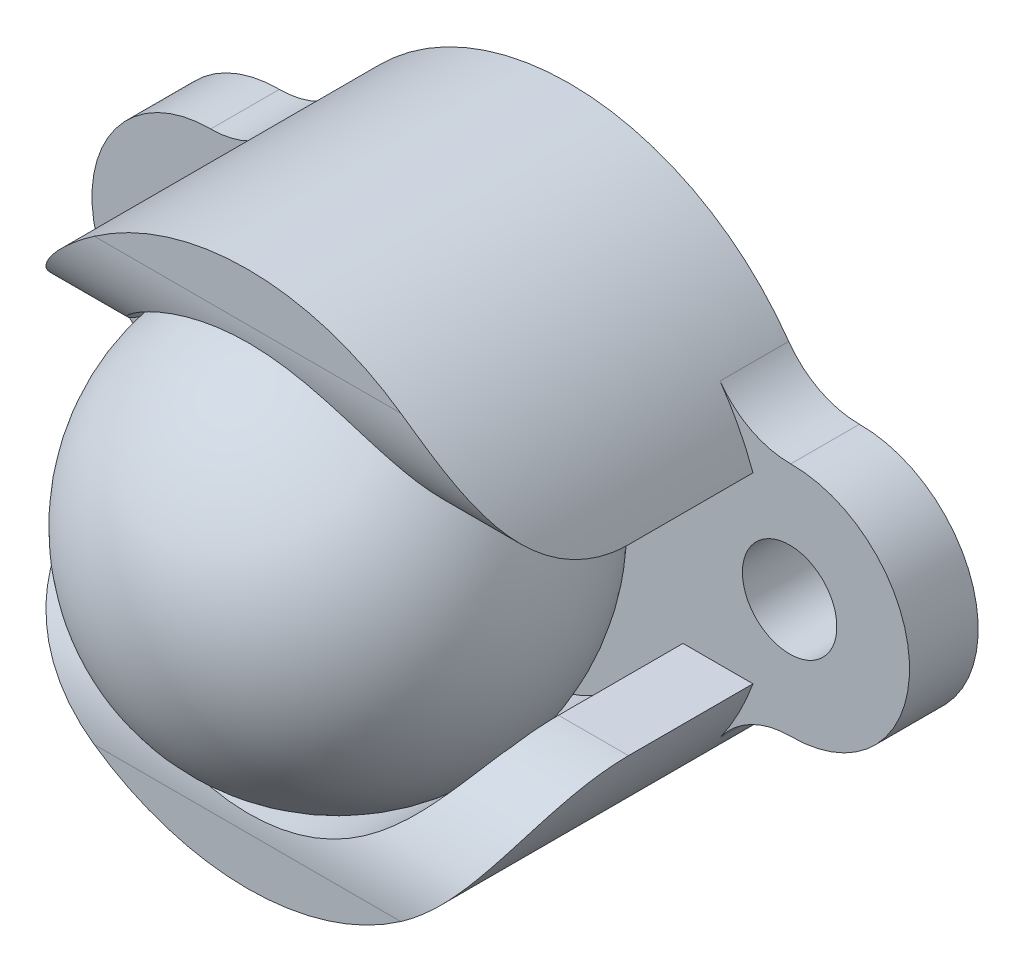
SolidWorks part; units mm, degrees
ref_plane "Front" through (0, 0, 0) normal (0, 0, 1) x (1, 0, 0)
ref_plane "Top" through (0, 0, 0) normal (0, 1, 0) x (1, 0, 0)
ref_plane "Right" through (0, 0, 0) normal (1, 0, 0) x (0, 0, -1)
sketch "Sketch1" plane through (0, 0, 0) normal (0, 0, 1) x (1, 0, 0)
  circle A0 centre (0, 0) radius 6.25
  circle A1 centre (0, 0) radius 4.75
  dimension "D1" = 12.5
  dimension "D2" = 1.5
extrude "Boss-Extrude1" add sketch "Sketch1" along normal blind 7.5
sketch "Sketch2" plane through (0, 0, 0) normal (0, 0, -1) x (-1, 0, 0)
  line L0 (-9.525, 9.3698) -> (-9.525, -6.2189) construction
  line L1 (9.525, 11.6916) -> (9.525, -7.2139) construction
  arc A0 (-6.7579, 2.7499) -> (-6.7579, -2.7499) centre (-6.775, 0) ccw
  arc A1 (6.7579, -2.7499) -> (6.7579, 2.7499) centre (6.775, 0) ccw
  circle A2 centre (0, 0) radius 6.25 construction
  arc A3 (5.1102, 3.5984) -> (-5.1102, 3.5984) centre (0, 0) ccw
  arc A4 (-5.1102, -3.5984) -> (5.1102, -3.5984) centre (0, 0) ccw
  arc A5 (6.7579, 2.7499) -> (5.1102, 3.5984) centre (6.7454, 4.7499) cw
  arc A6 (6.7579, -2.7499) -> (5.1102, -3.5984) centre (6.7454, -4.7499) ccw
  arc A7 (-6.7579, -2.7499) -> (-5.1102, -3.5984) centre (-6.7454, -4.7499) cw
  arc A8 (-6.7579, 2.7499) -> (-5.1102, 3.5984) centre (-6.7454, 4.7499) ccw
  circle A9 centre (0, 0) radius 2.9
  point P21 (-5.7122, -2.5363)
  dimension "D3" = 5.5
  dimension "D4" = 2
  dimension "D5" = 5.8
  dimension "D1" = 19.05
  dimension "D2" = 9.525
extrude "Boss-Extrude2" add sketch "Sketch2" against normal blind 1.6
sketch "Sketch3" [suppressed] plane through (0, 0, 7.5) normal (0, 0, 1) x (1, 0, 0)
  circle A0 centre (0, 0) radius 5.25
  dimension "D1" = 10.5
sketch "Sketch4" plane through (0, 0, 7.5) normal (0, 0, 1) x (1, 0, 0)
  line L1 (-8.5163, -2.1285) -> (8.5163, -2.1285)
  line L2 (-8.5163, -2.1285) -> (-8.5163, 2.1285)
  line L3 (-8.5163, 2.1285) -> (8.5163, 2.1285)
  line L4 (8.5163, -2.1285) -> (8.5163, 2.1285)
  line L5 (-8.5163, -2.1285) -> (8.5163, 2.1285) construction
  line L6 (-8.5163, 2.1285) -> (8.5163, -2.1285) construction
  point P0 (0, 0)
extrude "Cut-Extrude1" cut sketch "Sketch4" against normal up to surface (5.9 mm away) up to face at (-6.8587, 0, 1.6)
fillet "Fillet1" radius 3 4 edges at (-5.0614, -2.1285, 7.5) (5.0614, -2.1285, 7.5) (5.0614, 2.1285, 7.5) (-5.0614, 2.1285, 7.5)
sketch "Sketch5" plane through (0, 0, 0) normal (0, 0, -1) x (-1, 0, 0)
  circle A0 centre (-6.731, 0) radius 1.1
  circle A1 centre (6.731, 0) radius 1.1
  dimension "D2" = 2.2
  dimension "D1" = 13.462
  dimension "D3" = 6.731
extrude "Cut-Extrude2" cut sketch "Sketch5" against normal through all
sketch "Sketch6" plane through (0, 0, 0) normal (0, 1, 0) x (1, 0, 0)
  line L0 (0, -10.16) -> (-21.092, -10.16) construction
  line L1 (0, -0.635) -> (0, -10.16)
  arc A0 (0, -10.16) -> (0, -0.635) centre (0, -5.3975) ccw
  dimension "D1" = 9.525
  dimension "D2" = 10.16
revolve "Revolve1" add sketch "Sketch6" angle 360 about L1
equation "\"D2@Sketch2\"=\"D1@Sketch2\"/2"
equation "\"D3@Sketch5\"=\"D1@Sketch5\"/2"
